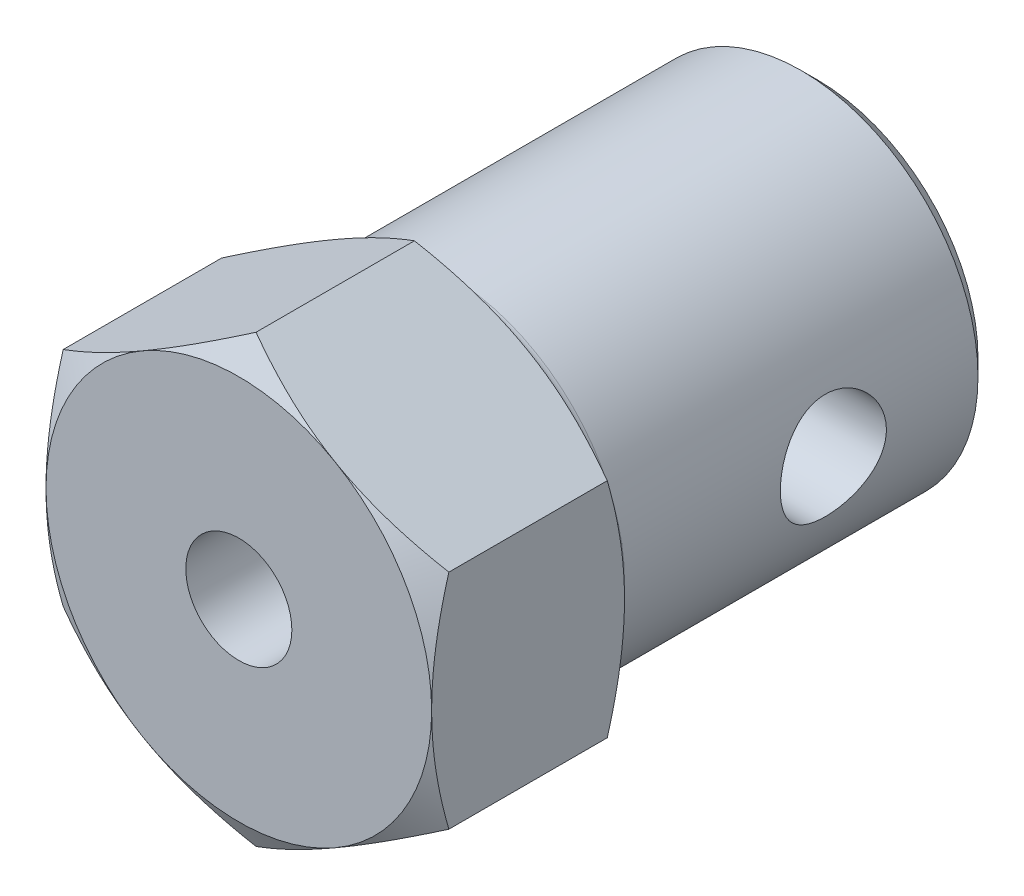
SolidWorks part; units mm, degrees
ref_plane "前视基准面" through (0, 0, 0) normal (0, 0, 1) x (1, 0, 0)
ref_plane "上视基准面" through (0, 0, 0) normal (0, 1, 0) x (1, 0, 0)
ref_plane "右视基准面" through (0, 0, 0) normal (1, 0, 0) x (0, 0, -1)
sketch "草图1" plane through (0, 0, 0) normal (0, 0, 1) x (1, 0, 0)
  line L0 (0, 6.9282) -> (0, 0) construction
  line L1 (-6, 3.4641) -> (-6, -3.4641)
  line L2 (-6, -3.4641) -> (0, -6.9282)
  line L3 (0, -6.9282) -> (6, -3.4641)
  line L4 (6, -3.4641) -> (6, 3.4641)
  line L5 (6, 3.4641) -> (0, 6.9282)
  line L6 (0, 6.9282) -> (-6, 3.4641)
  circle A0 centre (0, 0) radius 6 construction
  dimension "D2" = 12
extrude "凸台-拉伸1" add sketch "草图1" along normal blind 6
sketch "草图2" plane through (0, 0, 0) normal (0, 0, 1) x (1, 0, 0)
  circle A0 centre (0, 0) radius 5.5
  dimension "D1" = 11
extrude "凸台-拉伸2" add sketch "草图2" against normal blind 12
sketch "草图3" plane through (0, 0, -12) normal (0, 0, -1) x (-1, 0, 0)
  circle A0 centre (0, 0) radius 2
  dimension "D1" = 4
extrude "切除-拉伸1" cut sketch "草图3" against normal blind 12
fillet "圆角1" radius 0.5 1 edges at (5.5, 0, 0)
sketch "草图4" plane through (0, 0, 6) normal (0, 0, 1) x (1, 0, 0)
  circle A0 centre (0, 0) radius 0.9312
hole_wizard "M4 螺纹孔1" positions "草图5" profile "草图6" tap size "M4" standard "GB"
sketch "草图5" plane through (0, 0, 6) normal (0, 0, 1) x (1, 0, 0)
  point P0 (0, 0)
sketch "草图6" plane through (0, 0, 6) normal (1, 0, 0) x (0, -1, 0)
  line L0 (0, 0) -> (0, 10.1)
  line L1 (0, 10.1) -> (1.65, 10.1)
  line L2 (1.65, 10.1) -> (1.65, 0)
  line L5 (1.65, 0) -> (0, 0)
  line L10 (0, 10.1) -> (-1.65, 10.1) construction
  line L11 (0, -6.35) -> (0, 107.95) construction
  dimension "螺纹孔钻头直径" = 3.3
  dimension "螺纹孔钻头深度" = 10.1
  dimension "导头角度" = 180
cosmetic thread "孔螺蚊线1" parameters "D1"=8, "D2"=4
chamfer "倒角1" distance 0.5 angle 45 1 edges at (5.5, 0, -12)
sketch "草图7" plane through (0, 0, 6) normal (0, 0, 1) x (1, 0, 0)
  circle A0 centre (0, 0) radius 6 construction
  circle A1 centre (0, 0) radius 6
extrude "切除-拉伸2" cut sketch "草图7" against normal up to surface (6 mm away) draft 60 flip side to cut up to face at (5.2321, 3.0207, 0)
sketch "草图8" plane through (0, 0, 0) normal (0, 0, 1) x (1, 0, 0)
  circle A0 centre (0, 0) radius 6 construction
  circle A1 centre (0, 0) radius 6
extrude "切除-拉伸3" cut sketch "草图8" against normal up to surface (6 mm away) draft 60 flip side to cut
sketch "草图9" plane through (0, 0, 0) normal (1, 0, 0) x (0, 0, -1)
  line L0 (0, 0) -> (15.682, 0) construction
  line L1 (12, -5) -> (12, 5) construction
  circle A0 centre (7, 0) radius 2.767
  dimension "D1" = 5
hole_wizard "M4 螺纹孔3" positions "草图18" profile "草图19" tap size "M4" standard "GB"
sketch "草图18" plane through (0, 0, 0) normal (1, 0, 0) x (0, 0, -1)
  point P0 (7, 0)
sketch "草图19" plane through (0, 0, -7) normal (0, 1, 0) x (0, 0, 1)
  line L0 (0, 0) -> (0, 11.5)
  line L1 (0, 11.5) -> (1.65, 11.5)
  line L2 (1.65, 11.5) -> (1.65, 0)
  line L5 (1.65, 0) -> (0, 0)
  line L10 (0, 11.5) -> (-1.65, 11.5) construction
  line L11 (0, -6.35) -> (0, 107.95) construction
  dimension "螺纹孔钻头直径" = 3.3
  dimension "螺纹孔钻头深度" = 11.5
  dimension "导头角度" = 180
cosmetic thread "孔螺蚊线3" parameters "D1"=5.7, "D2"=4
hole_wizard "M4 螺纹孔4" positions "草图20" profile "草图21" tap size "M4" standard "GB"
sketch "草图20" plane through (0, 0, 0) normal (1, 0, 0) x (0, 0, -1)
  point P0 (7, 0)
sketch "草图21" plane through (0, 0, -7) normal (0, 1, 0) x (0, 0, -1)
  line L0 (0, 0) -> (0, 9.2)
  line L1 (0, 9.2) -> (1.65, 9.2)
  line L2 (1.65, 9.2) -> (1.65, 0)
  line L5 (1.65, 0) -> (0, 0)
  line L10 (0, 9.2) -> (-1.65, 9.2) construction
  line L11 (0, -6.35) -> (0, 107.95) construction
  dimension "螺纹孔钻头直径" = 3.3
  dimension "螺纹孔钻头深度" = 9.2
  dimension "导头角度" = 180
cosmetic thread "孔螺蚊线4" parameters "D1"=5.7, "D2"=4
